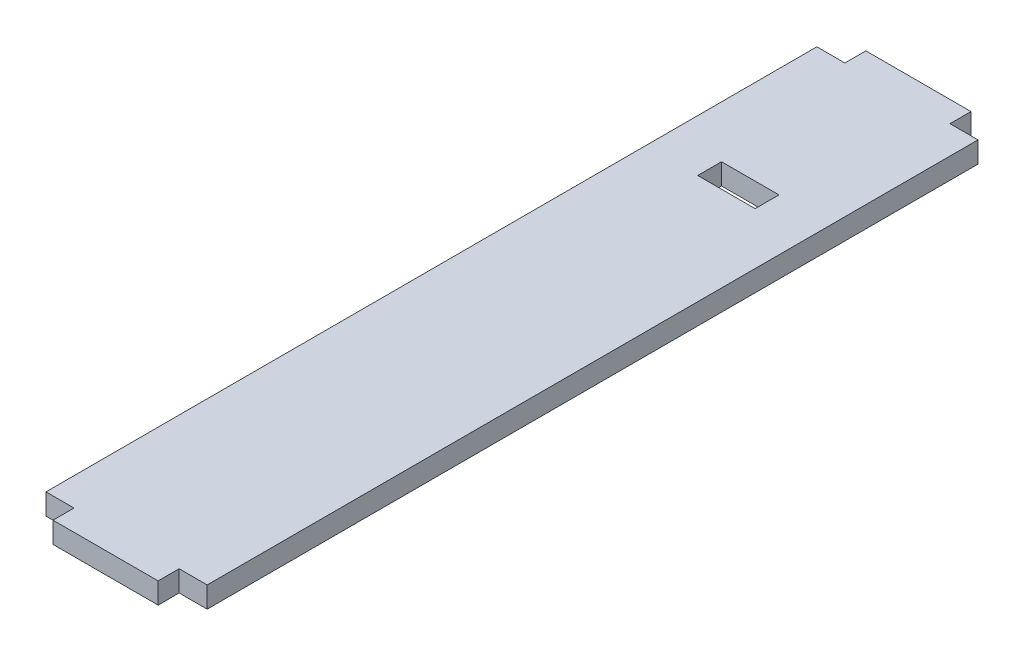
SolidWorks part; units mm, degrees
material "AISI 304"
ref_plane "Front Plane" through (0, 0, 0) normal (0, 0, 1) x (1, 0, 0)
ref_plane "Top Plane" through (0, 0, 0) normal (0, 1, 0) x (1, 0, 0)
ref_plane "Right Plane" through (0, 0, 0) normal (1, 0, 0) x (0, 0, -1)
sketch "Sketch1" plane through (0, 0, 0) normal (0, 1, 0) x (1, 0, 0)
  line L0 (3.75, 27.5) -> (5.75, 27.5)
  line L1 (-5.75, -27.5) -> (-3.75, -27.5)
  line L2 (-5.75, -27.5) -> (-5.75, -16.6)
  line L3 (-5.75, 27.5) -> (-3.75, 27.5)
  line L4 (5.75, -27.5) -> (5.75, -14.1)
  line L5 (-5.75, -27.5) -> (5.75, 27.5) construction
  line L6 (-5.75, 27.5) -> (5.75, -27.5) construction
  line L8 (3.75, 27.5) -> (3.75, 29)
  line L9 (3.75, 29) -> (-3.75, 29)
  line L10 (-3.75, 27.5) -> (-3.75, 29)
  line L12 (-3.75, -27.5) -> (-3.75, -29)
  line L13 (-3.75, -29) -> (3.75, -29)
  line L14 (3.75, -27.5) -> (3.75, -29)
  line L15 (3.75, -27.5) -> (5.75, -27.5)
  line L16 (-5.75, -14.9) -> (-5.75, 27.5)
  line L21 (5.75, -12.4) -> (5.75, 27.5)
  line L26 (0, 0) -> (0, 53.4412) construction
  line L31 (-5.75, -16.6) -> (-5.75, -14.9)
  line L32 (-2.05, 15.3) -> (2.05, 15.3)
  line L33 (-2.05, 15.3) -> (-2.05, 17)
  line L34 (-2.05, 17) -> (2.05, 17)
  line L35 (2.05, 15.3) -> (2.05, 17)
  line L36 (-2.05, 15.3) -> (2.05, 17) construction
  line L37 (-2.05, 17) -> (2.05, 15.3) construction
  line L38 (5.75, -12.4) -> (5.75, -14.1)
  point P0 (0, 0)
  point P23 (0, 16.15)
  dimension "D1" = 7.5
  dimension "D2" = 2
  dimension "D3" = 2
  dimension "D4" = 1.5
  dimension "D5" = 2
  dimension "D6" = 2
  dimension "D7" = 1.5
  dimension "D8" = 55
  dimension "D11" = 1.7
  dimension "D12" = 3.7
  dimension "D13" = 12
extrude "Boss-Extrude1" add sketch "Sketch1" along normal blind 1.5
